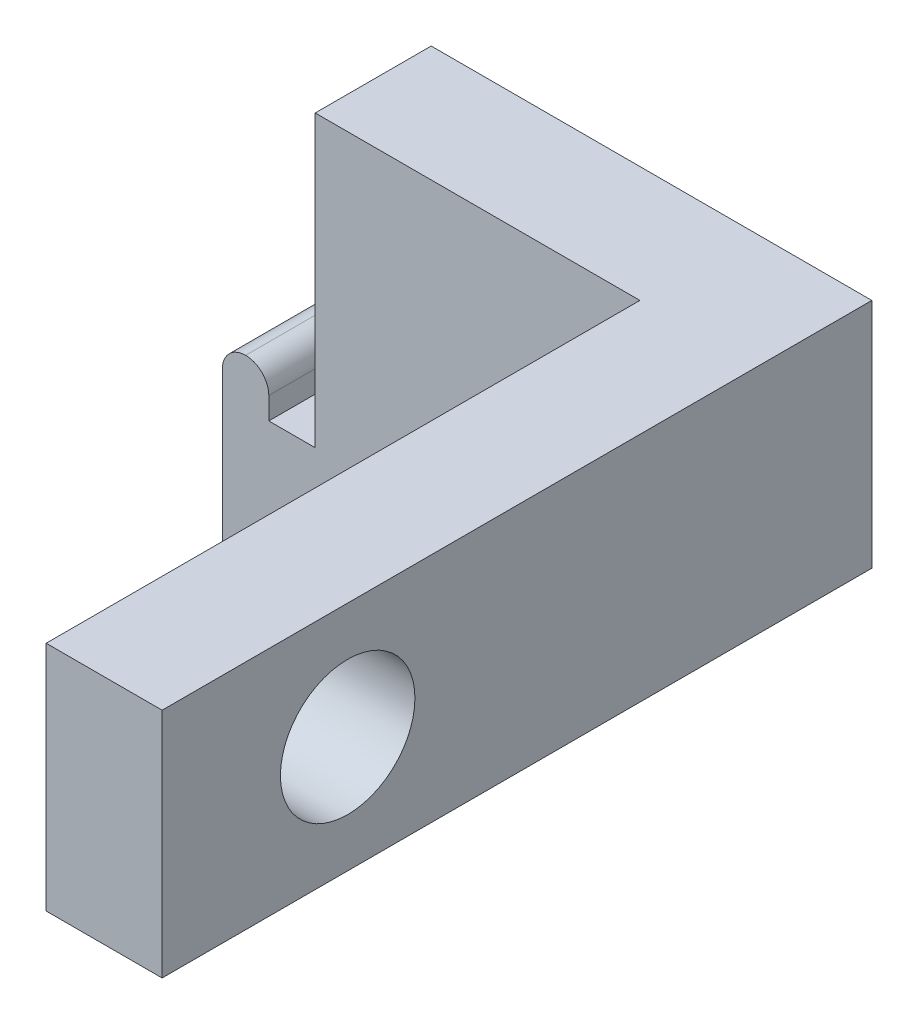
SolidWorks part; units mm, degrees
ref_plane "Front Plane" through (0, 0, 0) normal (0, 0, 1) x (1, 0, 0)
ref_plane "Top Plane" through (0, 0, 0) normal (0, 1, 0) x (1, 0, 0)
ref_plane "Right Plane" through (0, 0, 0) normal (1, 0, 0) x (0, 0, -1)
sketch "Sketch1" plane through (0, 0, 0) normal (0, 1, 0) x (1, 0, 0)
  line L0 (0, 0) -> (0, 31.75)
  line L1 (0, 31.75) -> (-22.86, 31.75)
  line L2 (-22.86, 31.75) -> (-22.86, 25.4)
  line L3 (-22.86, 25.4) -> (-6.35, 25.4)
  line L4 (-6.35, 25.4) -> (-6.35, 0)
  line L5 (-6.35, 0) -> (0, 0)
  dimension "D1" = 25.4
  dimension "D2" = 16.51
  dimension "D3" = 6.35
  dimension "D4" = 6.35
extrude "Boss-Extrude1" add sketch "Sketch1" along normal blind 12.7
sketch "Sketch3" plane through (0, 0, -31.75) normal (0, 0, -1) x (-1, 0, 0)
  line L0 (22.86, 12.7) -> (24.13, 12.7)
  line L3 (29.21, -0.6985) -> (29.21, -12.0015)
  line L5 (17.78, -12.0015) -> (17.78, 0)
  line L6 (0, 0) -> (22.86, 0) construction
  line L7 (17.78, 0) -> (22.86, 0)
  line L8 (22.86, 0) -> (22.86, 12.7)
  line L9 (17.78, -12.0015) -> (24.13, -12.0015)
  line L10 (24.13, -12.0015) -> (24.13, -9.525)
  line L11 (24.13, -9.525) -> (26.67, -9.525)
  line L12 (26.67, -9.525) -> (26.67, -12.0015)
  line L13 (26.67, -12.0015) -> (29.21, -12.0015)
  line L15 (24.13, 12.7) -> (24.13, -3.175)
  line L16 (24.13, -3.175) -> (26.67, -3.175)
  line L17 (26.67, -3.175) -> (26.67, -0.6985)
  line L18 (26.67, -0.6985) -> (29.21, -0.6985)
  line L19 (26.67, -9.525) -> (26.67, -3.175) construction
  point P3 (26.67, -6.35)
  point P4 (29.21, -6.35)
  point P17 (22.86, 6.35)
  dimension "D1" = 2.54
  dimension "D2" = 11.303
  dimension "D3" = 6.35
  dimension "D4" = 12.7
  dimension "D5" = 2.54
  dimension "D6" = 17.78
  dimension "D7" = 6.35
extrude "Boss-Extrude2" add sketch "Sketch3" against normal blind 6.35
fillet "Fillet1" radius 1.27 1 edges at (-26.67, -0.6985, -28.575)
fillet "Fillet2" radius 1.27 3 edges at (-26.67, -12.0015, -28.575) (-29.21, -12.0015, -28.575) (-29.21, -0.6985, -28.575)
sketch "Sketch4" plane through (0, 0, 0) normal (0, 0, 1) x (1, 0, 0)
  line L1 (-6.35, 0) -> (0, 0)
  line L2 (-6.35, 0) -> (-6.35, 12.7)
  line L3 (-6.35, 12.7) -> (0, 12.7)
  line L4 (0, 0) -> (0, 12.7)
extrude "Boss-Extrude3" add sketch "Sketch4" along normal blind 7.112
sketch "Sketch5" plane through (0, 0, 0) normal (1, 0, 0) x (0, 0, -1)
  circle A0 centre (3.048, 6.35) radius 3.683
  dimension "D1" = 22.352
extrude "Cut-Extrude1" cut sketch "Sketch5" against normal through all both and the other way through all
